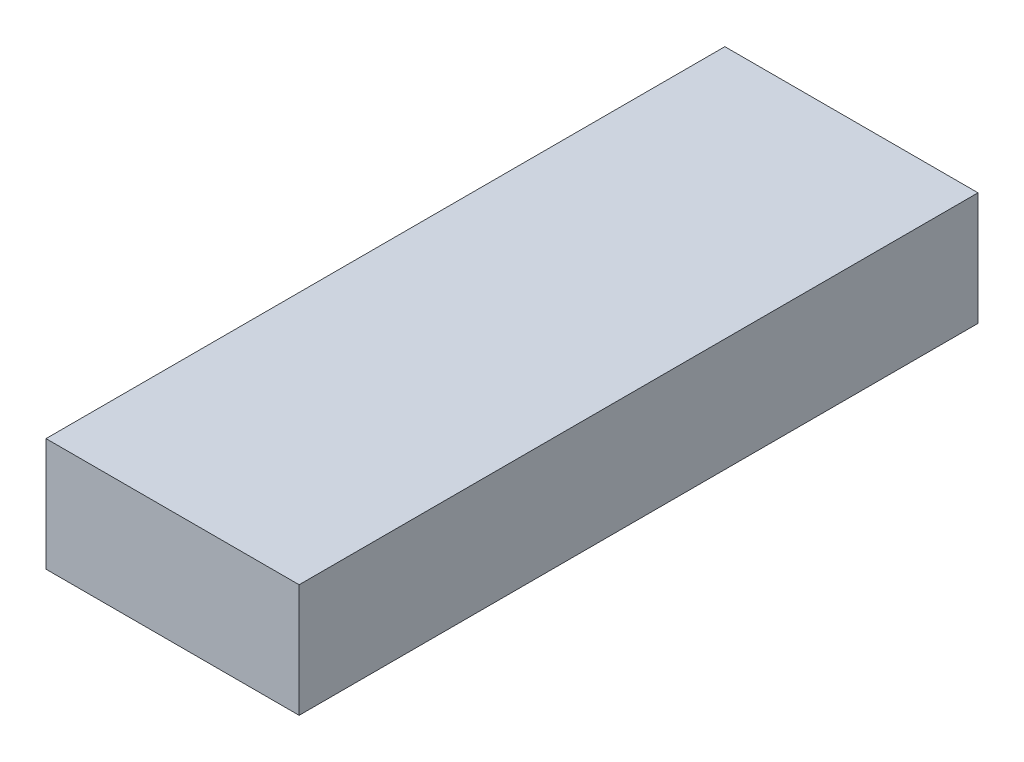
SolidWorks part; units mm, degrees
ref_plane "Front Plane" through (0, 0, 0) normal (1, 0, 0) x (0, 1, 0)
ref_plane "Top Plane" through (0, 0, 0) normal (0, 0, 1) x (0, 1, 0)
ref_plane "Right Plane" through (0, 0, 0) normal (0, 1, 0) x (-1, 0, 0)
sketch "Sketch1" plane through (0, 0, 0) normal (0, 0, 1) x (0, 1, 0)
  line L1 (-8.3312, -18.6436) -> (8.3312, -18.6436)
  line L2 (-8.3312, -18.6436) -> (-8.3312, 18.6436)
  line L3 (-8.3312, 18.6436) -> (8.3312, 18.6436)
  line L4 (8.3312, -18.6436) -> (8.3312, 18.6436)
  line L5 (-8.3312, -18.6436) -> (8.3312, 18.6436) construction
  line L6 (-8.3312, 18.6436) -> (8.3312, -18.6436) construction
  point P0 (0, 0)
  dimension "D1" = 16.6624
  dimension "D2" = 37.2872
extrude "Boss-Extrude1" add sketch "Sketch1" along normal mid plane 100
